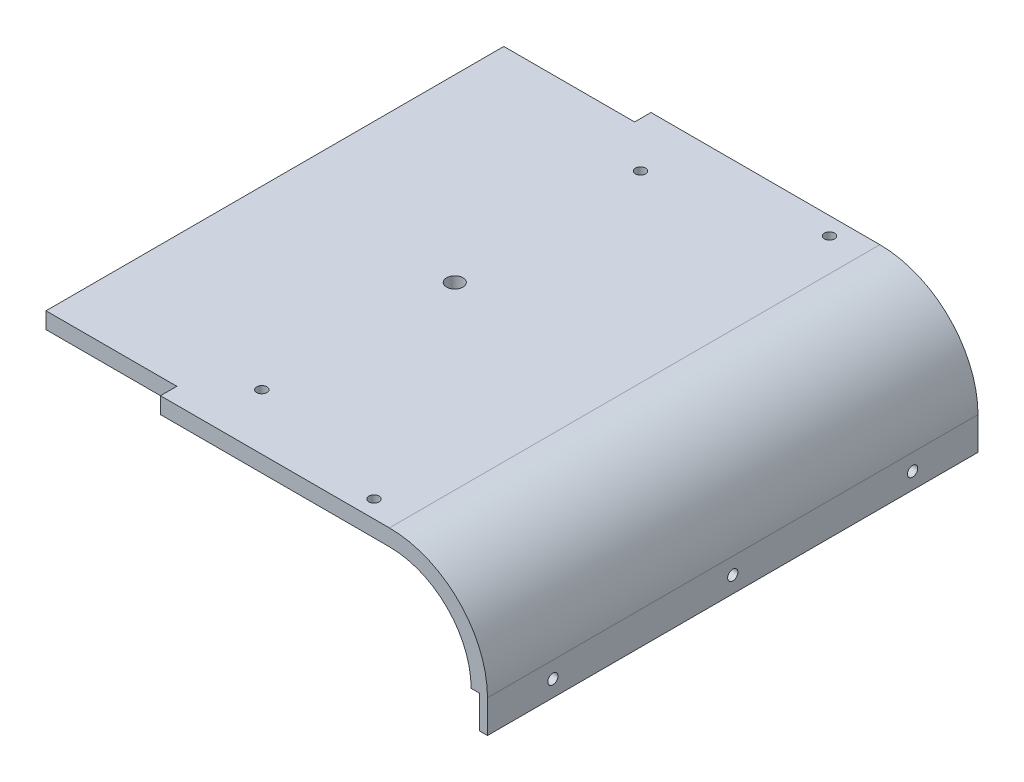
SolidWorks part; units mm, degrees
ref_plane "Front Plane" through (0, 0, 0) normal (0, 0, 1) x (1, 0, 0)
ref_plane "Top Plane" through (0, 0, 0) normal (0, 1, 0) x (1, 0, 0)
ref_plane "Right Plane" through (0, 0, 0) normal (1, 0, 0) x (0, 0, -1)
sketch "Sketch1" plane through (0, 0, 0) normal (0, 0, 1) x (1, 0, 0)
  line L0 (-139.7, 0) -> (139.7, 0)
  line L1 (139.7, 0) -> (139.7, -152.4) construction
  line L2 (139.7, -76.2) -> (215.9, -76.2) construction
  line L3 (-139.7, -12.7) -> (139.7, -12.7)
  line L4 (-139.7, 0) -> (-139.7, -12.7)
  line L5 (215.9, -76.2) -> (203.2, -76.2)
  circle A0 centre (139.7, -76.2) radius 76.2 construction
  arc A1 (139.7, 0) -> (215.9, -76.2) centre (139.7, -76.2) cw
  arc A2 (139.7, -12.7) -> (203.2, -76.2) centre (139.7, -76.2) cw
  point P4 (0, 0)
  dimension "D1" = 152.4
  dimension "D2" = 355.6
  dimension "D3" = 12.7
extrude "Boss-Extrude1" add sketch "Sketch1" along normal blind 190.5 and the other way blind 190.5
sketch "Sketch2" plane through (0, -76.2, 0) normal (0, -1, 0) x (1, 0, 0)
  line L0 (203.2, 190.5) -> (215.9, 190.5) construction
  line L1 (209.55, 190.5) -> (215.9, 190.5)
  line L2 (209.55, 190.5) -> (209.55, -190.5)
  line L3 (209.55, -190.5) -> (215.9, -190.5)
  line L4 (215.9, 190.5) -> (215.9, -190.5)
extrude "Boss-Extrude2" add sketch "Sketch2" along normal blind 25.4
sketch "Sketch3" plane through (215.9, 0, 0) normal (1, 0, 0) x (0, 0, -1)
  line L0 (-190.5, -88.9) -> (190.5, -88.9) construction
  line L1 (-190.5, -101.6) -> (-190.5, -76.2) construction
  line L2 (190.5, -101.6) -> (190.5, -76.2) construction
  line L3 (0, -76.2) -> (0, -101.6) construction
  line L4 (190.5, -76.2) -> (-190.5, -76.2) construction
  line L5 (190.5, -101.6) -> (-190.5, -101.6) construction
  line L6 (139.7, -76.2) -> (139.7, -101.6) construction
  line L7 (-139.7, -76.2) -> (-139.7, -101.6) construction
  circle A0 centre (-139.7, -88.9) radius 3.9687
  circle A1 centre (0, -88.9) radius 3.9687
  circle A2 centre (139.7, -88.9) radius 3.9687
  dimension "D3" = 7.9375
  dimension "D1" = 139.7
  dimension "D2" = 139.7
extrude "Cut-Extrude1" cut sketch "Sketch3" against normal blind 25.4
sketch "Sketch4" plane through (0, 0, 0) normal (0, 1, 0) x (1, 0, 0)
  circle A0 centre (0, 0) radius 6.35
  dimension "D1" = 12.7
extrude "Cut-Extrude2" cut sketch "Sketch4" against normal blind 17.78
sketch "Sketch5" plane through (0, 0, 0) normal (0, 1, 0) x (1, 0, 0)
  line L0 (139.7, 0) -> (114.3, 0) construction
  line L1 (139.7, 190.5) -> (139.7, -190.5) construction
  line L2 (-139.7, 190.5) -> (-139.7, -190.5) construction
  line L3 (-2.794, 0) -> (-2.794, -147.066) construction
  line L4 (114.3, 177.8) -> (114.3, -177.8) construction
  line L5 (-114.3, -177.8) -> (-114.3, 177.8) construction
  line L6 (139.7, -190.5) -> (-139.7, -190.5) construction
  line L7 (-114.3, 0) -> (-139.7, 0) construction
  line L8 (-114.3, 0) -> (0, 0) construction
  line L9 (0, 0) -> (114.3, 0) construction
  line L12 (-114.3, -177.8) -> (-139.7, -177.8)
  line L13 (-139.7, -177.8) -> (-139.7, -190.5)
  line L14 (-139.7, -190.5) -> (-38.1, -190.5)
  line L15 (-38.1, -190.5) -> (-38.1, -177.8)
  line L16 (-38.1, -177.8) -> (-114.3, -177.8)
  line L27 (-38.1, 190.5) -> (-38.1, 177.8)
  line L28 (-139.7, 190.5) -> (-38.1, 190.5)
  line L29 (-139.7, 177.8) -> (-139.7, 190.5)
  line L30 (-114.3, 177.8) -> (-139.7, 177.8)
  line L31 (-38.1, 177.8) -> (-114.3, 177.8)
  line L32 (139.7, 190.5) -> (-139.7, 190.5) construction
  line L33 (-2.794, 0) -> (-2.794, 147.066) construction
  circle A3 centre (114.3, -177.038) radius 3.937
  circle A4 centre (114.3, 176.784) radius 3.937
  circle A5 centre (-2.794, -147.066) radius 3.937
  circle A6 centre (-2.794, 147.066) radius 3.937
  point P11 (0, 0)
  point P15 (114.3, 0)
  point P18 (-114.3, 0)
  point P36 (0, 0)
  point P40 (0, -147.066)
  point P42 (0, 190.5)
  point P43 (0, 0)
  point P45 (-8.0579, 190.5)
  point P46 (-2.794, 147.8777)
  point P47 (0, 0)
  dimension "D3" = 13.462
  dimension "D2" = 7.874
  dimension "D8" = 7.874
  dimension "D1" = 12.7
  dimension "D4" = 101.6
  dimension "D5" = 13.716
  dimension "D6" = 114.3
  dimension "D7" = 43.434
  dimension "D9" = 136.906
extrude "Cut-Extrude3" cut sketch "Sketch5" against normal through all
